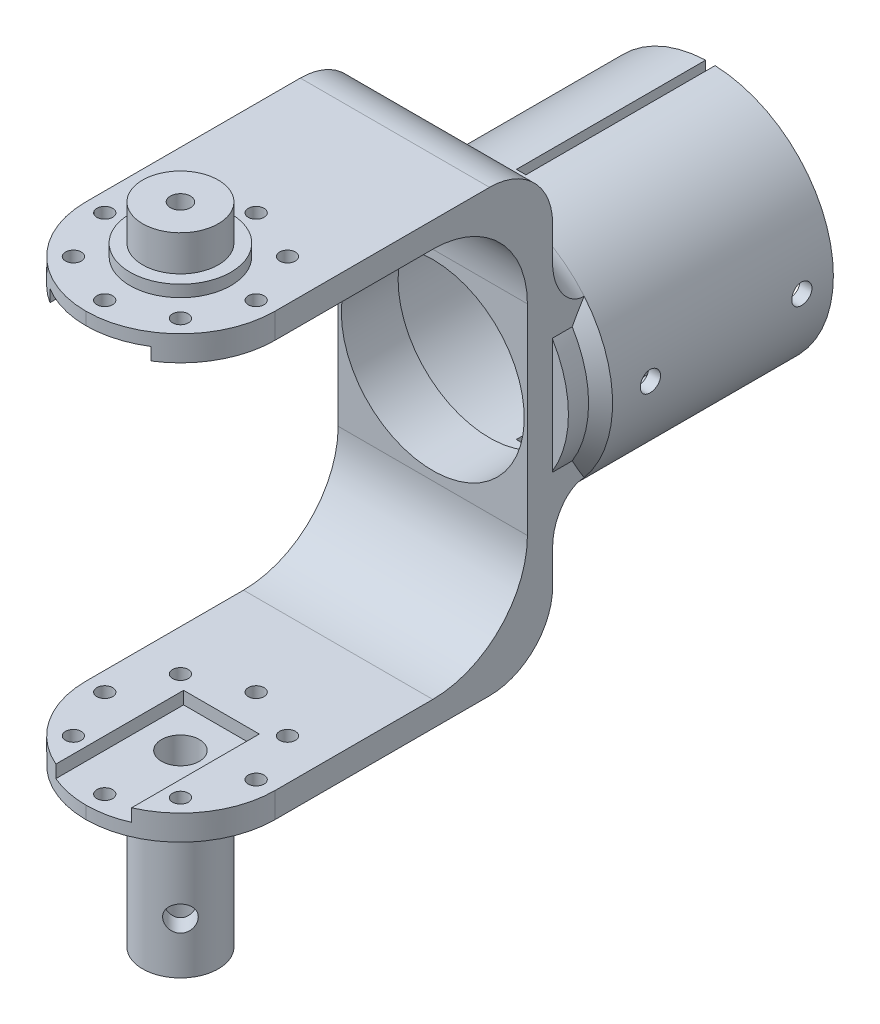
SolidWorks part; units mm, degrees
ref_plane "前视基准面" through (0, 0, 0) normal (0, 0, 1) x (1, 0, 0)
ref_plane "上视基准面" through (0, 0, 0) normal (0, 1, 0) x (1, 0, 0)
ref_plane "右视基准面" through (0, 0, 0) normal (1, 0, 0) x (0, 0, -1)
sketch "草图1" plane through (0, 0, 0) normal (1, 0, 0) x (0, 0, -1)
  line L0 (-27.5, 34.9) -> (31.5, 34.9)
  line L1 (-27.5, 30.9) -> (27.5, 30.9)
  line L2 (31.5, 34.9) -> (31.5, -34.9)
  line L3 (-27.5, -30.9) -> (27.5, -30.9)
  line L4 (27.5, 30.9) -> (27.5, -30.9)
  line L5 (-27.5, 30.9) -> (27.5, -30.9) construction
  line L6 (-27.5, -30.9) -> (27.5, 30.9) construction
  line L7 (-27.5, -34.9) -> (31.5, -34.9)
  line L8 (-27.5, 34.9) -> (-27.5, 30.9)
  line L9 (-27.5, -30.9) -> (-27.5, -34.9)
  point P0 (0, 0)
  dimension "D1" = 61.8
  dimension "D2" = 55
  dimension "D4" = 55
  dimension "D3" = 4
extrude "凸台-拉伸1" add sketch "草图1" along normal blind 30
sketch "草图4" plane through (0, 34.9, 0) normal (0, 1, 0) x (1, 0, 0)
  line L0 (30, 31.5) -> (30, -27.5) construction
  line L1 (30, -27.5) -> (0, -27.5) construction
  circle A0 centre (15, -12.5) radius 12 construction
  circle A1 centre (15, -0.5) radius 1.25
  circle A2 centre (15, -12.5) radius 12 construction
  circle A3 centre (23.4853, -4.0147) radius 1.25
  circle A4 centre (15, -12.5) radius 12 construction
  circle A5 centre (27, -12.5) radius 1.25
  circle A6 centre (15, -12.5) radius 12 construction
  circle A7 centre (23.4853, -20.9853) radius 1.25
  circle A8 centre (15, -12.5) radius 12 construction
  circle A9 centre (15, -24.5) radius 1.25
  circle A10 centre (15, -12.5) radius 12 construction
  circle A11 centre (6.5147, -20.9853) radius 1.25
  circle A12 centre (15, -12.5) radius 12 construction
  circle A13 centre (3, -12.5) radius 1.25
  circle A14 centre (15, -12.5) radius 12 construction
  circle A15 centre (6.5147, -4.0147) radius 1.25
  circle A16 centre (15, -12.5) radius 1.6
  point P31 (15, -12.5)
  dimension "D2" = 15
  dimension "D3" = 24
  dimension "D4" = 2.5
  dimension "D6" = 3.2
  dimension "D1" = 15
  dimension "D5" = 8
extrude "切除-拉伸1" cut sketch "草图4" against normal through all
fillet "圆角1" radius 15 6 edges at (0, 32.9, 27.5) (30, 32.9, 27.5) (30, -32.9, 27.5) (0, -32.9, 27.5) (15, -30.9, -27.5) (15, 30.9, -27.5)
fillet "圆角2" radius 10 2 edges at (15, -34.9, -31.5) (15, 34.9, -31.5)
sketch "草图5" plane through (0, 0, -31.5) normal (0, 0, -1) x (-1, 0, 0)
  line L0 (-30, -24.9) -> (-30, 24.9) construction
  circle A0 centre (-15, 0) radius 17.6
  circle A1 centre (-15, 0) radius 19.5
  dimension "D2" = 35.2
  dimension "D3" = 39
  dimension "D1" = 15
extrude "凸台-拉伸2" add sketch "草图5" along normal blind 40
sketch "草图7" plane through (0, 0, -71.5) normal (0, 0, -1) x (-1, 0, 0)
  line L1 (-15.75, 42.3131) -> (-14.25, 42.3131)
  line L2 (-15.75, 42.3131) -> (-15.75, -42.3131)
  line L3 (-15.75, -42.3131) -> (-14.25, -42.3131)
  line L4 (-14.25, 42.3131) -> (-14.25, -42.3131)
  line L5 (-15.75, 42.3131) -> (-14.25, -42.3131) construction
  line L6 (-15.75, -42.3131) -> (-14.25, 42.3131) construction
  point P0 (-15, 0)
  dimension "D1" = 1.5
extrude "切除-拉伸3" cut sketch "草图7" against normal blind 30
sketch "草图8" plane through (0, 0, 0) normal (1, 0, 0) x (0, 0, -1)
  line L0 (-977.5, 0) -> (49022.5, 0) construction
  line L1 (27.5, 15.9) -> (27.5, -15.9) construction
  line L2 (71.5, -19.4856) -> (71.5, 19.4856) construction
  line L3 (27.5, 15.9) -> (27.5, -15.9) construction
  circle A0 centre (66.5, 0) radius 1.6
  circle A1 centre (42.5, 0) radius 1.6
  point P5 (27.5, 0)
  dimension "D1" = 3.2
  dimension "D2" = 15
  dimension "D3" = 5
  dimension "D4" = 3.2
extrude "切除-拉伸4" cut sketch "草图8" along normal through all and the other way blind 8
sketch "草图10" plane through (0, 0, -31.5) normal (0, 0, -1) x (-1, 0, 0)
  circle A0 centre (-15, 0) radius 17.5
extrude "凸台-拉伸4" add sketch "草图10" along normal blind 5
chamfer "倒角2" distance 5 angle 45 2 edges at (34.5, 0, -31.5) (-4.5, 0, -31.5)
sketch "草图11" plane through (0, -34.9, 0) normal (0, -1, 0) x (1, 0, 0)
  circle A0 centre (15, 12.5) radius 8
  circle A1 centre (15, 12.5) radius 3
  dimension "D1" = 16
  dimension "D2" = 6
extrude "凸台-拉伸5" add sketch "草图11" along normal blind 25
sketch "草图12" plane through (0, -59.9, 0) normal (0, -1, 0) x (1, 0, 0)
  circle A0 centre (15, 12.5) radius 6
  dimension "D1" = 12
extrude "切除-拉伸5" cut sketch "草图12" against normal blind 23.15 flip side to cut
sketch "草图15" plane through (0, 34.9, 0) normal (0, 1, 0) x (1, 0, 0)
  circle A0 centre (15, -12.5) radius 8
  circle A1 centre (15, -12.5) radius 1.6
  dimension "D1" = 16
  dimension "D2" = 3.2
extrude "凸台-拉伸6" add sketch "草图15" along normal blind 7.5
sketch "草图16" plane through (0, 42.4, 0) normal (0, 1, 0) x (1, 0, 0)
  circle A0 centre (15, -12.5) radius 6
  dimension "D1" = 12
extrude "切除-拉伸6" cut sketch "草图16" against normal blind 5.65 flip side to cut
fillet "圆角3" radius 5 2 edges at (15, 19.5, -31.5) (15, -19.5, -31.5)
sketch "草图17" plane through (0, -34.9, 0) normal (0, -1, 0) x (1, 0, 0)
  circle A0 centre (15, 12.5) radius 3 construction
  circle A1 centre (15, 12.5) radius 3
extrude "切除-拉伸7" cut sketch "草图17" against normal blind 8
ref_plane "基准面1" through (0, 0, 12.5) normal (0, 0, -1) x (-1, 0, 0)
sketch "草图19" plane through (0, 0, 12.5) normal (0, 0, -1) x (-1, 0, 0)
  line L0 (0, 30.9) -> (-30, 30.9) construction
  line L1 (-7, 32.9) -> (-23, 32.9)
  line L2 (-7, 32.9) -> (-7, 28.9)
  line L3 (-7, 28.9) -> (-23, 28.9)
  line L4 (-23, 32.9) -> (-23, 28.9)
  line L5 (-7, 32.9) -> (-23, 28.9) construction
  line L6 (-7, 28.9) -> (-23, 32.9) construction
  line L7 (-30, -30.9) -> (0, -30.9) construction
  line L8 (-9, -32.9) -> (-21, -32.9)
  line L9 (-9, -32.9) -> (-9, -28.9)
  line L10 (-9, -28.9) -> (-21, -28.9)
  line L11 (-21, -32.9) -> (-21, -28.9)
  line L12 (-9, -32.9) -> (-21, -28.9) construction
  line L13 (-9, -28.9) -> (-21, -32.9) construction
  point P0 (-15, 30.9)
  point P7 (-15, -30.9)
  dimension "D1" = 12
  dimension "D2" = 4
  dimension "D3" = 16
  dimension "D4" = 4
extrude "切除-拉伸8" cut sketch "草图19" against normal blind 20 and the other way blind 6.5
sketch "草图20" plane through (0, 0, -36.5) normal (0, 0, -1) x (-1, 0, 0)
  circle A2 centre (-15, 0) radius 14.5
  circle A3 centre (-15, 0) radius 14.5
  dimension "D1" = 3
extrude "切除-拉伸9" cut sketch "草图20" against normal blind 20
ref_axis "基准轴1" through (15, -59.9, 12.5) along (0, 1, 0)
ref_plane "基准面2" through (1.25, 0, -1.25) normal (-0.7071, 0, 0.7071) x (0, 1, 0)
ref_plane "基准面3" through (0, -51.75, 0) normal (0, -1, 0) x (-1, 0, 0)
sketch "草图21" plane through (0, -51.75, 0) normal (0, -1, 0) x (-1, 0, 0)
  line L0 (-15, -12.5) -> (-15, 15.533)
  line L1 (-15, -12.5) -> (-33.3603, 9.381)
  dimension "D1" = 40
ref_plane "基准面4" through (33.3603, -51.75, -9.381) normal (0.6428, 0, -0.766) x (-0.766, 0, -0.6428)
sketch "草图22" plane through (33.3603, -51.75, -9.381) normal (0.6428, 0, -0.766) x (-0.766, 0, -0.6428)
  circle A0 centre (0, 0) radius 2
  dimension "D1" = 4
extrude "切除-拉伸10" [suppressed] cut sketch "草图22" against normal through all
ref_plane "基准面5" through (0, -51.75, 0) normal (0, -1, 0) x (-1, 0, 0)
sketch "草图23" plane through (0, -51.75, 0) normal (0, -1, 0) x (-1, 0, 0)
  line L0 (-15, -12.5) -> (-15, 15.533)
  line L1 (-15, -12.5) -> (1.1587, 3.6587)
  dimension "D1" = 45
ref_plane "基准面6" through (-1.1587, -51.75, -3.6587) normal (-0.7071, 0, -0.7071) x (-0.7071, 0, 0.7071)
sketch "草图24" plane through (-1.1587, -51.75, -3.6587) normal (-0.7071, 0, -0.7071) x (-0.7071, 0, 0.7071)
  circle A0 centre (0, 0) radius 2
  point P2 (0, 0)
  dimension "D1" = 4
extrude "切除-拉伸11" cut sketch "草图24" against normal through all
